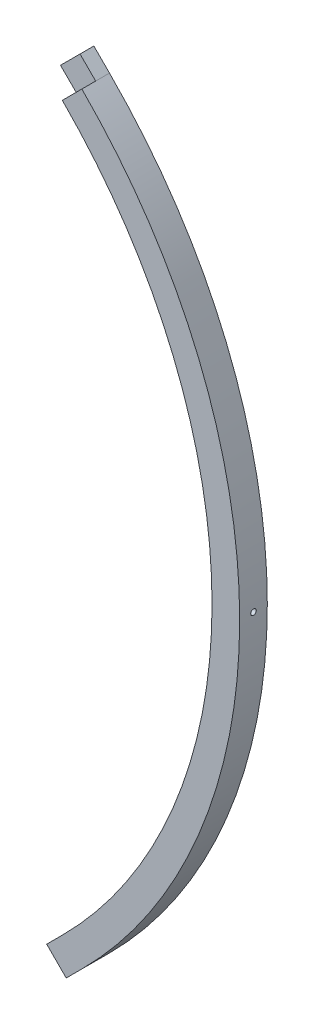
SolidWorks part; units mm, degrees
ref_plane "Ön Düzlem" through (0, 0, 0) normal (0, 0, 1) x (1, 0, 0)
ref_plane "Üst Düzlem" through (0, 0, 0) normal (0, 1, 0) x (1, 0, 0)
ref_plane "Sağ Düzlem" through (0, 0, 0) normal (1, 0, 0) x (0, 0, -1)
sketch "Çizim1" plane through (0, 0, 0) normal (0, 0, 1) x (1, 0, 0)
  circle A0 centre (0, 0) radius 185
  circle A1 centre (0, 0) radius 195
extrude "Yükseklik-Ekstrüzyon1" add sketch "Çizim1" along normal blind 10
sketch "Çizim2" plane through (0, 0, 0) normal (1, 0, 0) x (0, 0, -1)
  line L0 (0, 0) -> (-10, 0) construction
  line L1 (-10, 185) -> (-10, -185) construction
  circle A0 centre (-5, 0) radius 1
extrude "Kes-Ekstrüzyon1" cut sketch "Çizim2" against normal blind 240 and the other way blind 250
sketch "Çizim3" plane through (0, 0, 0) normal (0, 1, 0) x (1, 0, 0)
  line L0 (0, 0) -> (0, -10) construction
  line L1 (-195, -10) -> (195, -10) construction
  circle A0 centre (0, -5) radius 1
extrude "Kes-Ekstrüzyon2" cut sketch "Çizim3" against normal blind 240 and the other way blind 240
sketch "Çizim4" plane through (0, 0, 0) normal (0, 0, -1) x (-1, 0, 0)
  line L0 (250.0525, -250.0525) -> (-250.0525, 250.0525)
  line L1 (250.0525, -250.0525) -> (-250.0525, -250.0525)
  line L2 (250.0525, -250.0525) -> (250.0525, 250.0525)
  line L3 (250.0525, 250.0525) -> (-250.0525, 250.0525)
  line L4 (-250.0525, -250.0525) -> (-250.0525, 250.0525)
  line L5 (250.0525, -250.0525) -> (-250.0525, 250.0525) construction
  line L6 (250.0525, 250.0525) -> (-250.0525, -250.0525) construction
  line L7 (250.0525, 250.0525) -> (-250.0525, -250.0525)
  line L8 (137.6596, -137.6596) -> (130.5044, -130.5044) construction
  line L9 (137.6596, -137.6596) -> (130.5044, -130.5044)
  line L10 (130.5044, -130.5044) -> (134.082, -134.082)
  line L11 (137.6596, -137.6596) -> (134.082, -134.082)
  line L14 (134.082, -134.082) -> (130.5044, -130.5044)
  line L17 (-137.781, -137.781) -> (-130.5044, -130.5044)
  line L23 (-130.5044, -130.5044) -> (-134.1427, -134.1427)
  line L24 (-134.1427, -134.1427) -> (-132.3236, -132.3236)
  line L27 (-134.1427, -134.1427) -> (-137.781, -137.781)
  line L28 (-134.1427, -134.1427) -> (-137.781, -137.781)
  line L29 (-137.781, -137.781) -> (-135.9618, -135.9618)
  line L30 (-130.5044, -130.5044) -> (-137.781, -137.781)
  line L31 (-137.781, -137.781) -> (-130.5044, -130.5044)
  line L32 (-134.1427, -134.1427) -> (-137.781, -137.781)
  circle A0 centre (0, 0) radius 195
  circle A3 centre (0, 0) radius 185
  point P0 (0, 0)
  point P21 (0, 0)
  point P24 (0, 0)
  circle M20 centre (0, 0) radius 195
  circle M21 centre (0, 0) radius 185
extrude "Kes-Ekstrüzyon3" cut sketch "Çizim4" against normal blind 139 contours L0 L7 M21 | L7 L9 L0 M20 M21 | L7 L23 L17 L28 L0 L9 M21 M20 | L7 L0 M21 | L7 L0 M21 | L7 L0 M21 | L7 L0 M20 M21 region at (-135.7706, -139.7748, 0) region at (-137.8729, -133.8687, 0) region at (0, -111.039, 0) region at (-111.039, 0, 0) region at (111.039, 0, 0) region at (0, 192.1686, 0) region at (0, 111.039, 0)
sketch "Çizim6" plane through (0, 0, 0) normal (-0.7071, -0.7071, 0) x (0, 0, 1)
  line L0 (0, -185) -> (10, -185)
  line L1 (10, -185) -> (10, -195)
  line L2 (10, -195) -> (0, -195)
  line L3 (0, -195) -> (0, -185)
  line L4 (5, -185) -> (5, -195)
  line M5 (10, -195) -> (10, -185)
  line M6 (10, -185) -> (0, -185)
extrude "Yükseklik-Ekstrüzyon2" add sketch "Çizim6" along normal blind 8 contours L4 L2 M6 M5 region at (134.3503, -134.3503, 7.5)
sketch "Çizim7" plane through (0, 0, 0) normal (-0.7071, 0.7071, 0) x (0, 0, 1)
  line L0 (0, 195) -> (10, 195)
  line L1 (10, 195) -> (10, 185)
  line L2 (10, 185) -> (0, 185)
  line L3 (0, 185) -> (0, 195)
  line L4 (0, 195) -> (10, 195)
  line L5 (5, 195) -> (5, 185)
  line L6 (5, 185) -> (0, 185)
  line M2 (0, 195) -> (0, 185)
  line M3 (0, 185) -> (10, 185)
extrude "Yükseklik-Ekstrüzyon3" add sketch "Çizim7" along normal blind 8 contours L5 L4 M2 M3 region at (134.3503, 134.3503, 2.5)
